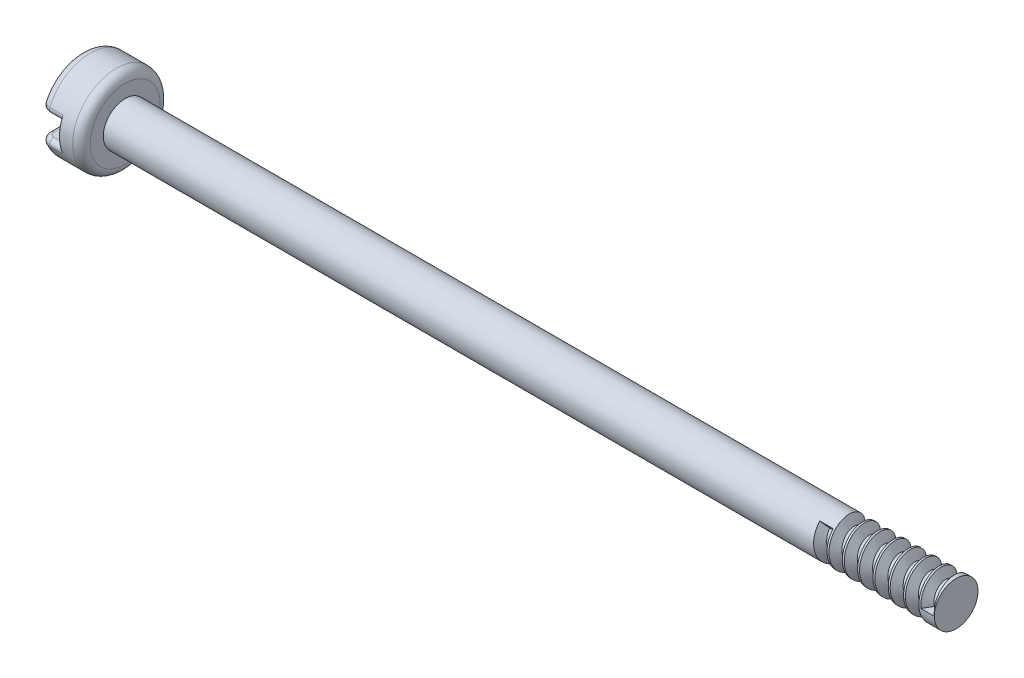
SolidWorks part; units mm, degrees
ref_plane "Front Plane" through (0, 0, 0) normal (0, 0, 1) x (1, 0, 0)
ref_plane "Top Plane" through (0, 0, 0) normal (0, 1, 0) x (1, 0, 0)
ref_plane "Right Plane" through (0, 0, 0) normal (1, 0, 0) x (0, 0, -1)
sketch "Sketch1" plane through (0, 0, 0) normal (0, 0, 1) x (1, 0, 0)
  line L0 (0, 0.8) -> (0, 0)
  line L1 (0, 0) -> (20, 0)
  line L2 (20, 0) -> (20, 0.5)
  line L3 (20, 0.5) -> (1, 0.5)
  line L4 (1, 0.5) -> (1, 0.8)
  line L5 (0.8, 1) -> (0.2, 1)
  arc A0 (1, 0.8) -> (0.8, 1) centre (0.8, 0.8) ccw
  arc A1 (0, 0.8) -> (0.2, 1) centre (0.2, 0.8) cw
  point P9 (1, 1)
  point P12 (0, 1)
  dimension "D5" = 0.2
  dimension "D1" = 1
  dimension "D2" = 1
  dimension "D3" = 0.5
  dimension "D4" = 20
revolve "Revolve1" add sketch "Sketch1" angle 360 about L1
thread "Thread1" pitch 0.35 method cut profile "Thread Profile1" start angle 0, offset 0, length 2.5, pitch 0.35, diameter 1
ref_plane "Plane1" through (20, 0, 0.5) normal (0, -1, 0) x (0, 0, 1)
sketch "Thread Profile1" plane through (20, 0, 0.5) normal (0, -1, 0) x (0, 0, 1)
  line L0 (0, 0) -> (0, 0.35) construction
  line L11 (0, 0) -> (0, 0.3062)
  line L12 (0, 0.3062) -> (-0.1894, 0.1969)
  line L13 (-0.1894, 0.1969) -> (-0.1894, 0.1094)
  line L15 (-0.1894, 0.1094) -> (0, 0)
  line L17 (-0.1894, 0.1531) -> (0, 0.1531) construction
  point P2 (0, 0)
  dimension "Pitch" = 0.35
  dimension "Profile_Angle" = 60
  dimension "Profile_Land" = 0.0875
  dimension "Profile_Height" = 0.1894
sketch "Sketch2" plane through (0, 0, 0) normal (-1, 0, 0) x (0, 0, 1)
  line L1 (-0.25, 0.625) -> (0.25, 0.625)
  line L2 (-0.25, 0.625) -> (-0.25, -0.625)
  line L3 (-0.25, -0.625) -> (0.25, -0.625)
  line L4 (0.25, 0.625) -> (0.25, -0.625)
  line L5 (-0.25, 0.625) -> (0.25, -0.625) construction
  line L6 (-0.25, -0.625) -> (0.25, 0.625) construction
  line L7 (-1.3929, 0.25) -> (1.3929, 0.25)
  line L8 (-1.3929, 0.25) -> (-1.3929, -0.25)
  line L9 (-1.3929, -0.25) -> (1.3929, -0.25)
  line L10 (1.3929, 0.25) -> (1.3929, -0.25)
  line L11 (-1.3929, 0.25) -> (1.3929, -0.25) construction
  line L12 (-1.3929, -0.25) -> (1.3929, 0.25) construction
  point P0 (0, 0)
  point P6 (0, 0)
  circle M3 centre (0, 0) radius 0.8
  dimension "D1" = 0.5
  dimension "D2" = 0.5
  dimension "D3" = 1.25
extrude "Cut-Extrude1" cut sketch "Sketch2" against normal blind 0.5 contours L8 L9 L7 M3 | L9 L2 L7 M3 | L4 L9 L7 M3 | L10 L7 L9 M3 | L2 L7 L4 L1 | L9 L2 L3 L4 | L2 L9 L4 L7 region at (0, 0.4375, 0) region at (0, 0, 0) region at (0, 0, -0.5185) region at (0, 0, 0.5185) region at (0, -0.4375, 0) region at (0, 0, -1.0897) region at (0, 0, 1.0897)
fillet "Fillet1" radius 0.1 20 edges at (0, 0.25, -0.505) (0.331, 0.25, -0.5987) (0, 0.25, 0.505) (0.0574, 0.25, 0.9064) (0, -0.25, 0.505) (0.0574, -0.25, 0.9064) (0, -0.25, -0.505) (0.331, -0.25, -0.5987) (0.35, 0.25, -0.9682) (0.25, 0.625, -0.25) (0.25, 0.625, 0.25) (0.25, 0.25, 0.25) (0.35, 0.25, 0.9682) (0.35, -0.25, 0.9682) (0.25, -0.25, 0.25) (0.25, -0.625, 0.25) (0.25, -0.625, -0.25) (0.25, -0.25, -0.25) (0.35, -0.25, -0.9682) (0.25, 0.25, -0.25)
